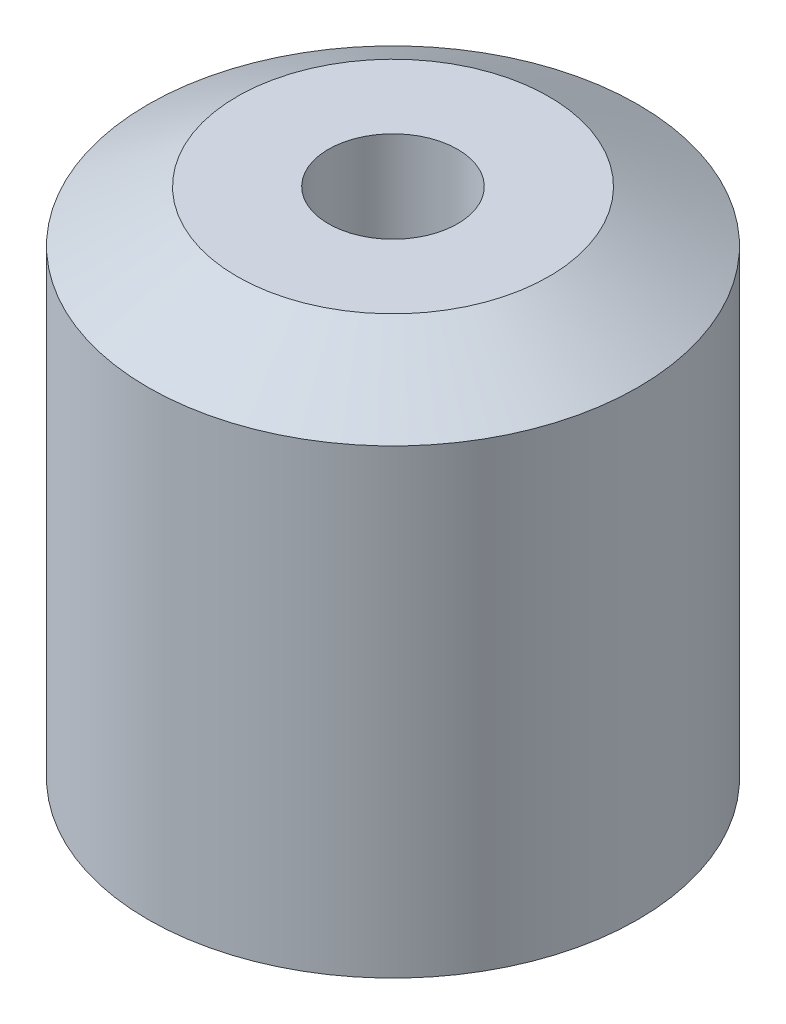
SolidWorks part; units mm, degrees
ref_plane "Front Plane" through (0, 0, 0) normal (0, 0, 1) x (1, 0, 0)
ref_plane "Top Plane" through (0, 0, 0) normal (0, 1, 0) x (1, 0, 0)
ref_plane "Right Plane" through (0, 0, 0) normal (1, 0, 0) x (0, 0, -1)
sketch "Sketch1" plane through (0, 0, 0) normal (1, 0, 0) x (0, 0, -1)
  line L0 (-5.5, 10.3453) -> (-5.5, 0)
  line L1 (-5.5, 0) -> (0, 0)
  line L4 (0, 11.5) -> (-3.5, 11.5)
  line L5 (-3.5, 11.5) -> (-5.5, 10.3453)
  line L6 (0, 11.5) -> (0, 0) construction
  line L7 (0, 11.5) -> (0, 0)
  dimension "D1" = 11.5
  dimension "D2" = 11
  dimension "D3" = 7
  dimension "D4" = 120
revolve "Revolve1" add sketch "Sketch1" angle 360 about L6
hole_wizard "CBORE for M2.5 SHCS1" positions "Sketch2" profile "Sketch4" counterbore size "M2.5" standard "ANSI Metric" end condition through all
sketch "Sketch2" plane through (0, 0, 0) normal (0, -1, 0) x (-1, 0, 0)
  point P0 (0, 0)
sketch "Sketch4" plane through (0, 0, 0) normal (1, 0, 0) x (0, 0, -1)
  line L0 (0, 0) -> (0, 11.5)
  line L1 (0, 11.5) -> (1.45, 11.5)
  line L3 (1.45, 11.5) -> (1.45, 2.5)
  line L4 (1.45, 2.5) -> (2.75, 2.5)
  line L5 (2.75, 2.5) -> (2.75, 0)
  line L7 (2.75, 0) -> (0, 0)
  line L11 (0, -6.35) -> (0, 107.95) construction
  dimension "Thru Hole Dia." = 2.9
  dimension "Thru Hole Depth" = 11.5
  dimension "C'Bore Dia." = 5.5
  dimension "C'Bore Depth" = 2.5
